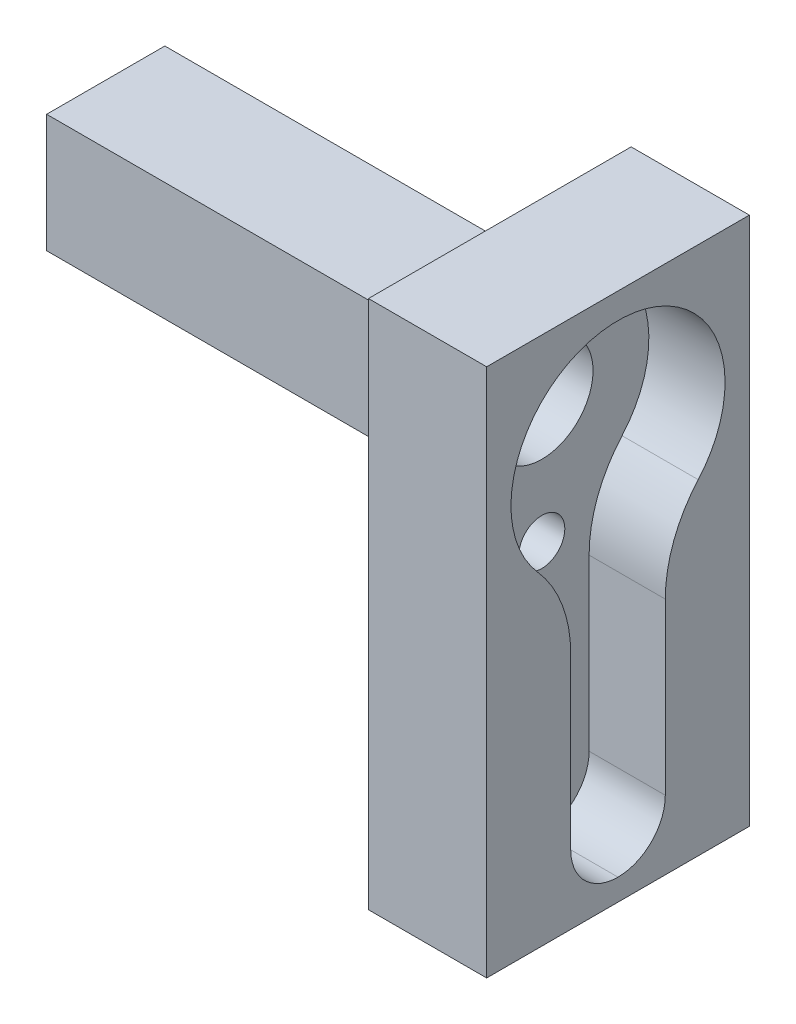
SolidWorks part; units mm, degrees
ref_plane "Front Plane" through (0, 0, 0) normal (0, 0, 1) x (1, 0, 0)
ref_plane "Top Plane" through (0, 0, 0) normal (0, 1, 0) x (1, 0, 0)
ref_plane "Right Plane" through (0, 0, 0) normal (1, 0, 0) x (0, 0, -1)
sketch "Sketch1" plane through (0, 0, 0) normal (1, 0, 0) x (0, 0, -1)
  line L1 (-10, 10) -> (10, 10)
  line L2 (-10, 10) -> (-10, -10)
  line L3 (-10, -10) -> (10, -10)
  line L4 (10, 10) -> (10, -10)
  line L5 (-10, 10) -> (10, -10) construction
  line L6 (-10, -10) -> (10, 10) construction
  point P0 (0, 0)
  dimension "D1" = 20
  dimension "D2" = 20
extrude "Boss-Extrude1" add sketch "Sketch1" along normal blind 20
sketch "Sketch2" plane through (20, 0, 0) normal (1, 0, 0) x (0, 0, -1)
  line L1 (-22.5, 35) -> (22.5, 35)
  line L2 (-22.5, 35) -> (-22.5, -35)
  line L3 (-22.5, -35) -> (22.5, -35)
  line L4 (22.5, 35) -> (22.5, -35)
  line L5 (-22.5, 35) -> (22.5, -35) construction
  line L6 (-22.5, -35) -> (22.5, 35) construction
  point P0 (0, 0)
  dimension "D1" = 45
  dimension "D2" = 70
extrude "Boss-Extrude2" add sketch "Sketch2" along normal blind 12
sketch "Sketch4" plane through (32, 0, 0) normal (1, 0, 0) x (0, 0, -1)
  line L0 (0, 7.65) -> (0, 8.1702) construction
  line L1 (7.65, 7.65) -> (-7.65, 7.65) construction
  line L17 (3.6, -26.55) -> (-3.6, -26.55) construction
  line L18 (-7.65, 7.65) -> (7.65, 7.65) construction
  line L22 (-7.65, 7.65) -> (-7.65, -27.55) construction
  line L23 (-7.65, -27.55) -> (7.65, -27.55) construction
  line L24 (7.65, 7.65) -> (7.65, -27.55) construction
  line L25 (-7.65, 7.65) -> (7.65, -27.55) construction
  line L26 (-7.65, -27.55) -> (7.65, 7.65) construction
  line L27 (3.6, -26.55) -> (3.6, -28.55) construction
  line L28 (3.6, -28.55) -> (-3.6, -28.55) construction
  line L29 (-3.6, -26.55) -> (-3.6, -28.55) construction
  line L30 (3.6, -26.55) -> (-3.6, -28.55) construction
  line L31 (3.6, -28.55) -> (-3.6, -26.55) construction
  line L34 (3.6, -28.55) -> (-3.6, -28.55)
  line L35 (-3.6, -28.55) -> (-3.6, -7.3118)
  line L36 (3.6, -28.55) -> (3.6, -7.3118)
  arc A1 (3.6, -6.75) -> (-3.6, -6.75) centre (0, 0) ccw construction
  arc A2 (3.6, -7.3118) -> (-3.6, -7.3118) centre (0, 0) ccw
  point P1 (0, -27.55)
  point P7 (0, -13.75)
  point P10 (0, 7.65)
  point P14 (0, -9.95)
  dimension "D1" = 15.3
  dimension "D5" = 2
  dimension "D2" = 15.3
  dimension "D3" = 35.2
  dimension "D4" = 7.2
extrude "Cut-Extrude1" cut sketch "Sketch4" against normal blind 5.8
fillet "Fillet1" radius 3.6 2 edges at (29.1, -28.55, 3.6) (29.1, -28.55, -3.6)
fillet "Fillet2" radius 10 2 edges at (29.1, -7.3118, 3.6) (29.1, -7.3118, -3.6)
sketch "Sketch5" plane through (0, 0, 0) normal (-1, 0, 0) x (0, 0, 1)
  circle A0 centre (0, 0) radius 3.9
  dimension "D1" = 7.8
extrude "Cut-Extrude2" cut sketch "Sketch5" against normal through all
sketch "Sketch6" plane through (26.2, 0, 0) normal (1, 0, 0) x (0, 0, -1)
  line L0 (0, -19.35) -> (0, 0) construction
  line L1 (0, -25.65) -> (0, -23.15) construction
  line L2 (0, -23.15) -> (0, -21.85) construction
  line L3 (0, -21.85) -> (0, -19.35) construction
  line L5 (0, 0) -> (1.164, 0) construction
  line L6 (0, 0) -> (0, -9.35) construction
  line L7 (0, -9.35) -> (1.164, -9.35) construction
  line L8 (1.164, 0) -> (1.164, -9.35) construction
  line L9 (0, 0) -> (1.164, -9.35) construction
  line L10 (0, -9.35) -> (1.164, 0) construction
  circle A0 centre (0, -20.6) radius 1.75
  circle A1 centre (0, -9.35) radius 1.75
  point P11 (0.582, -4.675)
  dimension "D5" = 3.5
  dimension "D6" = 9.35
  dimension "D7" = 3.5
  dimension "D1" = 19.35
  dimension "D2" = 2.5
  dimension "D3" = 1.3
  dimension "D4" = 2.5
extrude "Cut-Extrude3" cut sketch "Sketch6" against normal up to next
sketch "Sketch7" plane through (0, -35, 0) normal (0, -1, 0) x (1, 0, 0)
  line L1 (32, 22.5) -> (20, 22.5)
  line L2 (32, 22.5) -> (32, -22.5)
  line L3 (32, -22.5) -> (20, -22.5)
  line L4 (20, 22.5) -> (20, -22.5)
  line L5 (32, 22.5) -> (20, -22.5) construction
  line L6 (32, -22.5) -> (20, 22.5) construction
  point P5 (26, 0)
extrude "Cut-Extrude4" cut sketch "Sketch7" against normal blind 4.8
sketch "Sketch9" plane through (0, 35, 0) normal (0, 1, 0) x (1, 0, 0)
  line L1 (32, 22.5) -> (20, 22.5)
  line L2 (32, 22.5) -> (32, -22.5)
  line L3 (32, -22.5) -> (20, -22.5)
  line L4 (20, 22.5) -> (20, -22.5)
  line L5 (32, 22.5) -> (20, -22.5) construction
  line L6 (32, -22.5) -> (20, 22.5) construction
  point P4 (26, 0)
extrude "Cut-Extrude5" cut sketch "Sketch9" against normal blind 23.8
sketch "Sketch10" plane through (20, 0, 0) normal (-1, 0, 0) x (0, 0, 1)
  line L0 (-22.5, 11.2) -> (22.5, 11.2) construction
  line L1 (-10, 11.2) -> (-22.5, 11.2)
  line L2 (-10, 11.2) -> (-10, -30.2)
  line L3 (-10, -30.2) -> (-22.5, -30.2)
  line L4 (-22.5, 11.2) -> (-22.5, -30.2)
  line L5 (-10, 11.2) -> (-22.5, -30.2) construction
  line L6 (-10, -30.2) -> (-22.5, 11.2) construction
  line L7 (22.5, -30.2) -> (-22.5, -30.2) construction
  line L9 (10, 11.2) -> (22.5, 11.2)
  line L10 (10, 11.2) -> (10, -30.2)
  line L11 (10, -30.2) -> (22.5, -30.2)
  line L12 (22.5, 11.2) -> (22.5, -30.2)
  line L13 (10, 11.2) -> (22.5, -30.2) construction
  line L14 (10, -30.2) -> (22.5, 11.2) construction
  point P4 (-16.25, -9.5)
  point P13 (16.25, -9.5)
extrude "Cut-Extrude6" cut sketch "Sketch10" against normal blind 23.8
sketch "Sketch11" plane through (20, 0, 0) normal (-1, 0, 0) x (0, 0, 1)
  line L5 (-10, 11.2) -> (10, 11.2)
  line L6 (-10, 11.2) -> (-10, 10)
  line L7 (-10, 10) -> (10, 10)
  line L8 (10, 11.2) -> (10, 10)
  line L9 (-10, 11.2) -> (10, 10) construction
  line L10 (-10, 10) -> (10, 11.2) construction
  point P4 (0, 10.6)
extrude "Cut-Extrude7" cut sketch "Sketch11" against normal blind 23.8
sketch "Sketch12" plane through (0, 0, 0) normal (-1, 0, 0) x (0, 0, 1)
  line L1 (10, 10) -> (-10, 10)
  line L2 (10, 10) -> (10, -10)
  line L3 (10, -10) -> (-10, -10)
  line L4 (-10, 10) -> (-10, -10)
  line L5 (10, 10) -> (-10, -10) construction
  line L6 (10, -10) -> (-10, 10) construction
  circle A0 centre (0, 0) radius 3.9
  point P4 (0, 0)
extrude "Boss-Extrude3" add sketch "Sketch12" along normal blind 20
sketch "Sketch13" plane through (-20, 0, 0) normal (-1, 0, 0) x (0, 0, 1)
  line L8 (10.1, -10.1) -> (10.1, 10.1)
  line L9 (10.1, 10.1) -> (-10.1, 10.1)
  line L10 (-10.1, 10.1) -> (-10.1, -10.1)
  line L11 (-10.1, -10.1) -> (10.1, -10.1)
  line L12 (10.1, -10.1) -> (10.1, 10.1)
  line L13 (10.1, 10.1) -> (-10.1, 10.1)
  line L14 (-10.1, 10.1) -> (-10.1, -10.1)
  line L15 (-10.1, -10.1) -> (10.1, -10.1)
  circle A0 centre (0, 0) radius 3.9
  dimension "D1" = 0.1
extrude "Boss-Extrude4" add sketch "Sketch13" against normal up to surface (40 mm away) up to face at (20, -20.6, -1.75)
sketch "Sketch14" plane through (0, 10, 0) normal (0, 1, 0) x (1, 0, 0)
  line L1 (32, 10) -> (20, 10)
  line L2 (32, 10) -> (32, -10)
  line L3 (32, -10) -> (20, -10)
  line L4 (20, 10) -> (20, -10)
  line L5 (32, 10) -> (20, -10) construction
  line L6 (32, -10) -> (20, 10) construction
  point P4 (26, 0)
extrude "Boss-Extrude5" add sketch "Sketch14" along normal blind 0.1
sketch "Sketch17" plane through (-20, 0, 0) normal (-1, 0, 0) x (0, 0, 1)
  circle A0 centre (0, 0) radius 4.8309
extrude "Boss-Extrude8" add sketch "Sketch17" against normal blind 39
sketch "Sketch18" plane through (-20, 0, 0) normal (-1, 0, 0) x (0, 0, 1)
  line L5 (10.1, 10.1) -> (-15.5388, 10.1)
  line L6 (10.1, 10.1) -> (10.1, -36.522)
  line L7 (10.1, -36.522) -> (-15.5388, -36.522)
  line L8 (-15.5388, 10.1) -> (-15.5388, -36.522)
  line L9 (10.1, 10.1) -> (-15.5388, -36.522) construction
  line L10 (10.1, -36.522) -> (-15.5388, 10.1) construction
  point P4 (-2.7194, -13.211)
extrude "Cut-Extrude8" cut sketch "Sketch18" against normal blind 43
sketch "Sketch19" plane through (23, 0, 0) normal (-1, 0, 0) x (0, 0, 1)
  line L1 (4.5, 4.5) -> (-4.5, 4.5)
  line L2 (4.5, 4.5) -> (4.5, -4.5)
  line L3 (4.5, -4.5) -> (-4.5, -4.5)
  line L4 (-4.5, 4.5) -> (-4.5, -4.5)
  line L5 (4.5, 4.5) -> (-4.5, -4.5) construction
  line L6 (4.5, -4.5) -> (-4.5, 4.5) construction
  point P0 (0, 0)
  dimension "D1" = 9
  dimension "D2" = 9
extrude "Boss-Extrude9" add sketch "Sketch19" along normal blind 30
